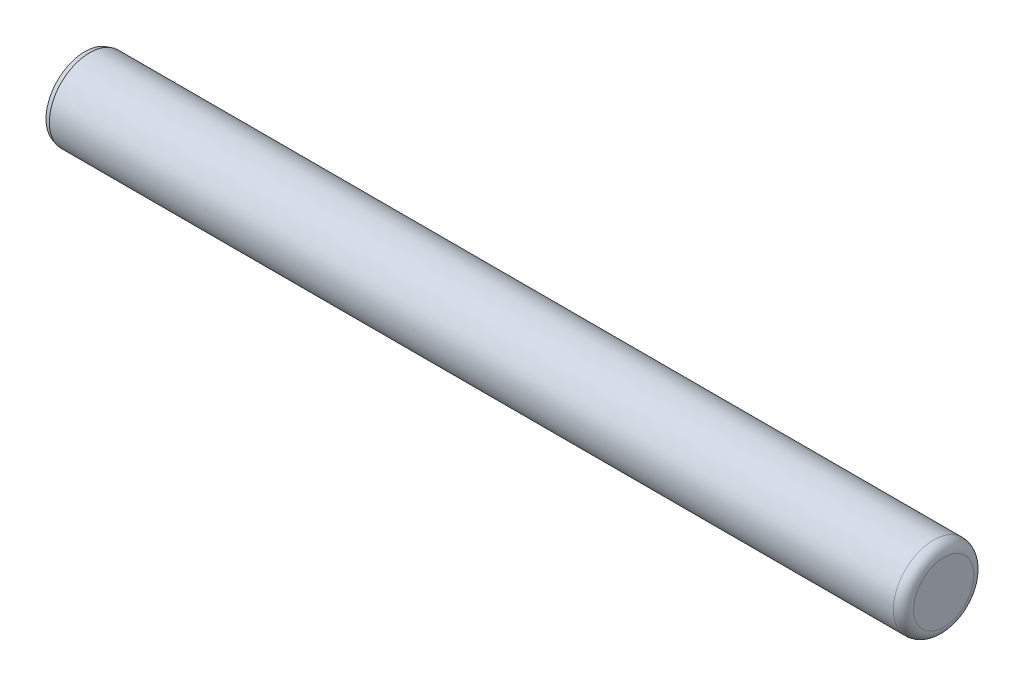
SolidWorks part; units mm, degrees
material "Alloy Steel"
ref_plane "Front" through (0, 0, 0) normal (0, 0, 1) x (1, 0, 0)
ref_plane "Top" through (0, 0, 0) normal (0, 1, 0) x (1, 0, 0)
ref_plane "Right" through (0, 0, 0) normal (1, 0, 0) x (0, 0, -1)
sketch "Sketch1" plane through (0, 0, 0) normal (1, 0, 0) x (0, 0, -1)
  circle A0 centre (0, 0) radius 9.525 construction
  point P3 (0, 9.525)
  dimension "Diameter" = 19.05
sketch "Sketch2" plane through (0, 0, 0) normal (0, 0, 1) x (1, 0, 0)
  line L0 (-101.6, 0) -> (101.6, 0) construction
  line L1 (101.6, 7.1374) -> (101.6, -0.6481) construction
  line L2 (-101.6, 9.2075) -> (-101.6, -9.2075) construction
  line L3 (-101.6, 9.2075) -> (-101.6, 9.525) construction
  line L4 (-101.6, -9.2075) -> (-101.6, -9.525) construction
  line L5 (-101.6, 9.2075) -> (-100.4927, 9.525) construction
  line L6 (-100.4927, 9.525) -> (99.2124, 9.525) construction
  arc A0 (99.2124, 9.525) -> (101.6, 7.1374) centre (99.2124, 7.1374) cw construction
  point P6 (-82.55, 0)
  point P8 (82.55, 0)
  point P23 (95.25, 9.525)
  dimension "Crown Radius" = 2.3876
  dimension "Length" = 203.2
  dimension "D1" = 19.05
  dimension "D2" = 19.05
  dimension "Point Diameter" = 18.415
  dimension "D3" = 16
  dimension "Crown Height" = 6.35
sketch "Sketch3" plane through (0, 0, 0) normal (0, 0, 1) x (1, 0, 0)
  line L0 (101.6, 7.1374) -> (101.6, -0.6481) construction
  line L1 (-100.4927, 9.525) -> (99.2124, 9.525) construction
  line L2 (-101.6, 9.2075) -> (-100.4927, 9.525) construction
  line L3 (-101.6, 9.2075) -> (-101.6, -9.2075) construction
  line L4 (-101.6, 0) -> (101.6, 0) construction
  line L5 (101.6, 7.1374) -> (101.6, 0)
  line L6 (-100.4927, 9.525) -> (99.2124, 9.525)
  line L7 (-101.6, 9.2075) -> (-100.4927, 9.525)
  line L8 (-101.6, 9.2075) -> (-101.6, 0)
  line L9 (-101.6, 0) -> (101.6, 0)
  arc A0 (101.6, 7.1374) -> (99.2124, 9.525) centre (99.2124, 7.1374) ccw construction
  arc A1 (101.6, 7.1374) -> (99.2124, 9.525) centre (99.2124, 7.1374) ccw
revolve "Revolve1" add sketch "Sketch3" angle 360 about L0
equation "\"D1@Sketch2\" = \"Diameter@Sketch1\""
equation "\"D2@Sketch2\" = \"Diameter@Sketch1\""
